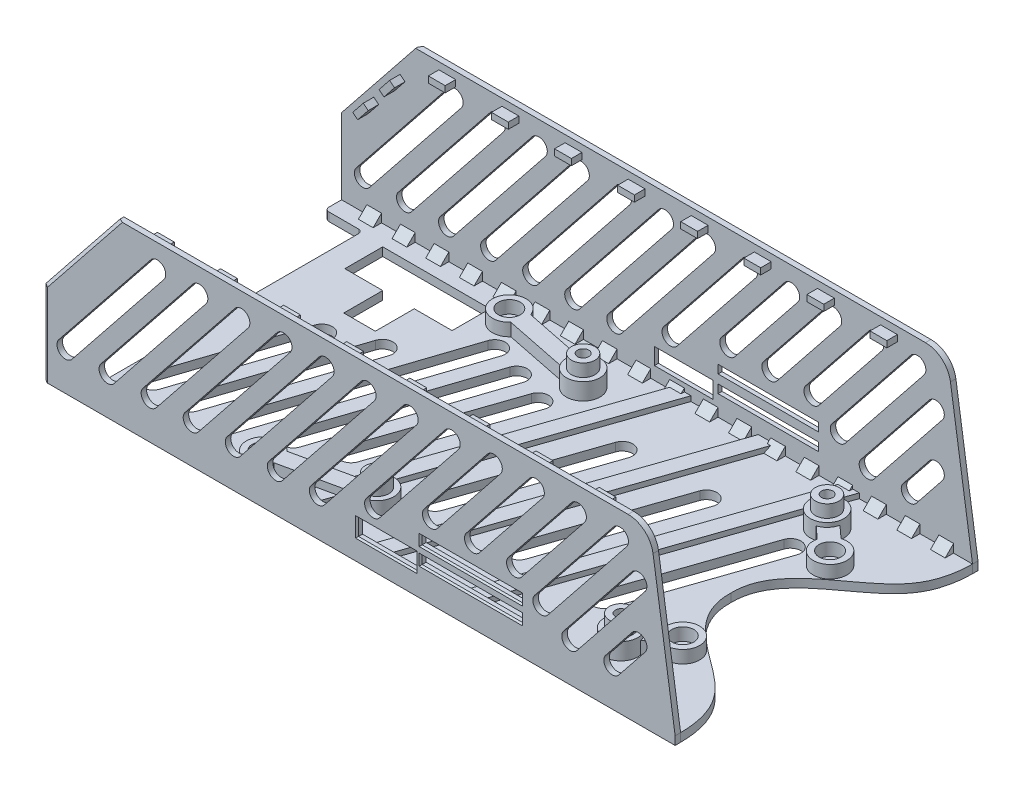
SolidWorks part; units mm, degrees
material "PPS"
ref_plane "前视基准面" through (0, 0, 0) normal (0, 0, 1) x (1, 0, 0)
ref_plane "上视基准面" through (0, 0, 0) normal (0, 1, 0) x (1, 0, 0)
ref_plane "右视基准面" through (0, 0, 0) normal (1, 0, 0) x (0, 0, -1)
sketch "草图1" plane through (0, 0, 0) normal (0, 1, 0) x (1, 0, 0)
  line L1 (-38.5883, 74.1339) -> (111.4117, 74.1339)
  line L2 (-38.5883, 74.1339) -> (-38.5883, 2.1339)
  line L3 (-38.5883, 2.1339) -> (111.4117, 2.1339)
  line L4 (111.4117, 74.1339) -> (111.4117, 2.1339)
  dimension "D1" = 72
  dimension "D2" = 150
extrude "底板" add sketch "草图1" against normal blind 2 contours L2 L1 L4 L3
sketch "草图2" plane through (0, 0, 0) normal (0, 1, 0) x (1, 0, 0)
  circle A3 centre (28.7548, 13.929) radius 4
  circle A4 centre (86.7548, 13.929) radius 4
  circle A5 centre (86.7548, 62.929) radius 4
  circle A6 centre (28.7548, 62.929) radius 4
  dimension "D1" = 2
  dimension "D2" = 2
extrude "板卡固定柱" add sketch "草图2" along normal blind 7
sketch "螺母孔" plane through (0, -2, 0) normal (0, -1, 0) x (1, 0, 0)
  line L0 (88.256, -11.329) -> (85.2537, -11.329)
  line L1 (30.256, -11.329) -> (27.2537, -11.329)
  line L2 (27.2537, -11.329) -> (25.7526, -13.929)
  line L3 (25.7526, -13.929) -> (27.2537, -16.529)
  line L4 (27.2537, -16.529) -> (30.256, -16.529)
  line L5 (30.256, -16.529) -> (31.7571, -13.929)
  line L6 (31.7571, -13.929) -> (30.256, -11.329)
  line L7 (85.2537, -11.329) -> (83.7526, -13.929)
  line L8 (83.7526, -13.929) -> (85.2537, -16.529)
  line L9 (85.2537, -16.529) -> (88.256, -16.529)
  line L10 (88.256, -16.529) -> (89.7571, -13.929)
  line L11 (89.7571, -13.929) -> (88.256, -11.329)
  line L12 (88.256, -60.329) -> (85.2537, -60.329)
  line L13 (85.2537, -60.329) -> (83.7526, -62.929)
  line L14 (83.7526, -62.929) -> (85.2537, -65.529)
  line L15 (85.2537, -65.529) -> (88.256, -65.529)
  line L16 (88.256, -65.529) -> (89.7571, -62.929)
  line L17 (89.7571, -62.929) -> (88.256, -60.329)
  line L18 (30.256, -60.329) -> (27.2537, -60.329)
  line L19 (27.2537, -60.329) -> (25.7526, -62.929)
  line L20 (25.7526, -62.929) -> (27.2537, -65.529)
  line L21 (27.2537, -65.529) -> (30.256, -65.529)
  line L22 (30.256, -65.529) -> (31.7571, -62.929)
  line L23 (31.7571, -62.929) -> (30.256, -60.329)
  circle A0 centre (28.7548, -13.929) radius 2.6 construction
  circle A1 centre (28.7548, -13.929) radius 4 construction
  circle A2 centre (86.7548, -13.929) radius 2.6 construction
  circle A3 centre (86.7548, -62.929) radius 2.6 construction
  circle A4 centre (28.7548, -62.929) radius 2.6 construction
  dimension "D1" = 2
  dimension "D2" = 2
extrude "m2.5螺母孔槽" cut sketch "螺母孔" against normal blind 5
sketch "草图4" plane through (0, 3, 0) normal (0, -1, 0) x (1, 0, 0)
  circle A0 centre (28.7548, -13.929) radius 1.35
  circle A1 centre (28.7548, -13.929) radius 4 construction
  circle A2 centre (86.7548, -13.929) radius 1.35
  circle A3 centre (86.7548, -62.929) radius 1.35
  circle A4 centre (28.7548, -62.929) radius 1.35
  dimension "D1" = 2
  dimension "D2" = 2
extrude "m2.5通孔" cut sketch "草图4" against normal up to next
sketch "草图6" plane through (0, 7, 0) normal (0, 1, 0) x (1, 0, 0)
  circle A0 centre (28.7548, 13.929) radius 4
  circle A1 centre (28.7548, 13.929) radius 2.7944
  circle A2 centre (86.7548, 13.929) radius 4
  circle A3 centre (86.7548, 13.929) radius 2.7944
  circle A4 centre (86.7548, 62.929) radius 4
  circle A5 centre (86.7548, 62.929) radius 2.7944
  circle A6 centre (28.7548, 62.929) radius 4
  circle A7 centre (28.7548, 62.929) radius 2.7944
  dimension "D1" = 2
  dimension "D2" = 2
extrude "切除-拉伸3" cut sketch "草图6" against normal blind 3
sketch "侧边" plane through (0, 0, -74.1339) normal (0, 0, -1) x (-1, 0, 0)
  line L0 (-74.7943, 6.8381) -> (-50.9153, 6.8381)
  line L1 (-111.4117, 0) -> (38.5883, 0)
  line L6 (-74.7943, 10.8959) -> (-50.9153, 10.8959)
  line L8 (-74.7943, 10.8959) -> (-74.7943, 8.8959)
  line L9 (-74.7943, 4.8381) -> (-50.9153, 4.8381)
  line L10 (-50.9153, 4.8381) -> (-50.9153, 6.8381)
  line L11 (-74.7943, 8.8959) -> (-50.9153, 8.8959)
  line L12 (-74.7943, 6.8381) -> (-74.7943, 4.8381)
  line L13 (-50.9153, 8.8959) -> (-50.9153, 10.8959)
  line L16 (-49.6686, 3.0554) -> (-35.7948, 3.0554)
  line L17 (-35.7948, 3.0554) -> (-35.7948, 7)
  line L18 (-35.7948, 7) -> (-49.6686, 7)
  line L19 (-49.6686, 7) -> (-49.6686, 3.0554)
  line L21 (38.5883, -2) -> (38.5883, 0) construction
  line L22 (20.9589, 40) -> (-100.2254, 40)
  line L23 (-106.1585, 34.8932) -> (-111.4117, 0)
  line L25 (38.5883, 0) -> (38.5883, 17.9447)
  line L26 (38.5883, 17.9447) -> (20.9589, 40)
  line L27 (33.5375, 7.0719) -> (11.6845, 34.4113) construction
  line L28 (31.9753, 5.8231) -> (10.1222, 33.1625)
  line L29 (35.0998, 8.3206) -> (13.2467, 35.66)
  line L30 (23.5375, 7.0719) -> (1.6845, 34.4113) construction
  line L31 (21.9753, 5.8231) -> (0.1222, 33.1625)
  line L32 (25.0998, 8.3206) -> (3.2467, 35.66)
  line L33 (13.5375, 7.0719) -> (-8.3155, 34.4113) construction
  line L34 (11.9753, 5.8231) -> (-9.8778, 33.1625)
  line L35 (15.0998, 8.3206) -> (-6.7533, 35.66)
  line L36 (3.5375, 7.0719) -> (-18.3155, 34.4113) construction
  line L37 (1.9753, 5.8231) -> (-19.8778, 33.1625)
  line L38 (5.0998, 8.3206) -> (-16.7533, 35.66)
  line L39 (-6.4625, 7.0719) -> (-28.3155, 34.4113) construction
  line L40 (-8.0247, 5.8231) -> (-29.8778, 33.1625)
  line L41 (-4.9002, 8.3206) -> (-26.7533, 35.66)
  line L42 (-16.4625, 7.0719) -> (-38.3155, 34.4113) construction
  line L43 (-18.0247, 5.8231) -> (-39.8778, 33.1625)
  line L44 (-14.9002, 8.3206) -> (-36.7533, 35.66)
  line L45 (-26.4625, 7.0719) -> (-48.3155, 34.4113) construction
  line L46 (-28.0247, 5.8231) -> (-49.8778, 33.1625)
  line L47 (-24.9002, 8.3206) -> (-46.7533, 35.66)
  line L48 (-39.5843, 10.9775) -> (-58.3155, 34.4113) construction
  line L49 (-41.1466, 9.7287) -> (-59.8778, 33.1625)
  line L50 (-38.0221, 12.2262) -> (-56.7533, 35.66)
  line L51 (-53.3306, 15.6642) -> (-68.3155, 34.4113) construction
  line L52 (-54.8928, 14.4155) -> (-69.8778, 33.1625)
  line L53 (-51.7683, 16.913) -> (-66.7533, 35.66)
  line L54 (-63.3306, 15.6642) -> (-78.3155, 34.4113) construction
  line L55 (-64.8928, 14.4155) -> (-79.8778, 33.1625)
  line L56 (-61.7683, 16.913) -> (-76.7533, 35.66)
  line L57 (-73.3306, 15.6642) -> (-88.3155, 34.4113) construction
  line L58 (-74.8928, 14.4155) -> (-89.8778, 33.1625)
  line L59 (-71.7683, 16.913) -> (-86.7533, 35.66)
  line L60 (-79.5843, 10.9775) -> (-98.3155, 34.4113) construction
  line L61 (-81.1466, 9.7287) -> (-99.8778, 33.1625)
  line L62 (-78.0221, 12.2262) -> (-96.7533, 35.66)
  line L63 (-86.4625, 7.0719) -> (-102.6962, 27.3811) construction
  line L64 (-88.0247, 5.8231) -> (-104.2584, 26.1324)
  line L65 (-84.9002, 8.3206) -> (-101.1339, 28.6299)
  line L66 (-96.4625, 7.0719) -> (-102.7062, 14.8831) construction
  line L67 (-98.0247, 5.8231) -> (-104.2685, 13.6344)
  line L68 (-94.9002, 8.3206) -> (-101.144, 16.1319)
  arc A0 (-100.2254, 40) -> (-106.1585, 34.8932) centre (-100.2254, 34) ccw
  arc A1 (31.9753, 5.8231) -> (35.0998, 8.3206) centre (33.5375, 7.0719) ccw
  arc A2 (13.2467, 35.66) -> (10.1222, 33.1625) centre (11.6845, 34.4113) ccw
  arc A3 (21.9753, 5.8231) -> (25.0998, 8.3206) centre (23.5375, 7.0719) ccw
  arc A4 (3.2467, 35.66) -> (0.1222, 33.1625) centre (1.6845, 34.4113) ccw
  arc A5 (11.9753, 5.8231) -> (15.0998, 8.3206) centre (13.5375, 7.0719) ccw
  arc A6 (-6.7533, 35.66) -> (-9.8778, 33.1625) centre (-8.3155, 34.4113) ccw
  arc A7 (1.9753, 5.8231) -> (5.0998, 8.3206) centre (3.5375, 7.0719) ccw
  arc A8 (-16.7533, 35.66) -> (-19.8778, 33.1625) centre (-18.3155, 34.4113) ccw
  arc A9 (-8.0247, 5.8231) -> (-4.9002, 8.3206) centre (-6.4625, 7.0719) ccw
  arc A10 (-26.7533, 35.66) -> (-29.8778, 33.1625) centre (-28.3155, 34.4113) ccw
  arc A11 (-18.0247, 5.8231) -> (-14.9002, 8.3206) centre (-16.4625, 7.0719) ccw
  arc A12 (-36.7533, 35.66) -> (-39.8778, 33.1625) centre (-38.3155, 34.4113) ccw
  arc A13 (-28.0247, 5.8231) -> (-24.9002, 8.3206) centre (-26.4625, 7.0719) ccw
  arc A14 (-46.7533, 35.66) -> (-49.8778, 33.1625) centre (-48.3155, 34.4113) ccw
  arc A15 (-41.1466, 9.7287) -> (-38.0221, 12.2262) centre (-39.5843, 10.9775) ccw
  arc A16 (-56.7533, 35.66) -> (-59.8778, 33.1625) centre (-58.3155, 34.4113) ccw
  arc A17 (-54.8928, 14.4155) -> (-51.7683, 16.913) centre (-53.3306, 15.6642) ccw
  arc A18 (-66.7533, 35.66) -> (-69.8778, 33.1625) centre (-68.3155, 34.4113) ccw
  arc A19 (-64.8928, 14.4155) -> (-61.7683, 16.913) centre (-63.3306, 15.6642) ccw
  arc A20 (-76.7533, 35.66) -> (-79.8778, 33.1625) centre (-78.3155, 34.4113) ccw
  arc A21 (-74.8928, 14.4155) -> (-71.7683, 16.913) centre (-73.3306, 15.6642) ccw
  arc A22 (-86.7533, 35.66) -> (-89.8778, 33.1625) centre (-88.3155, 34.4113) ccw
  arc A23 (-81.1466, 9.7287) -> (-78.0221, 12.2262) centre (-79.5843, 10.9775) ccw
  arc A24 (-96.7533, 35.66) -> (-99.8778, 33.1625) centre (-98.3155, 34.4113) ccw
  arc A25 (-88.0247, 5.8231) -> (-84.9002, 8.3206) centre (-86.4625, 7.0719) ccw
  arc A26 (-101.1339, 28.6299) -> (-104.2584, 26.1324) centre (-102.6962, 27.3811) ccw
  arc A27 (-98.0247, 5.8231) -> (-94.9002, 8.3206) centre (-96.4625, 7.0719) ccw
  arc A28 (-101.144, 16.1319) -> (-104.2685, 13.6344) centre (-102.7062, 14.8831) ccw
  point P2 (22.611, 20.7416)
  point P31 (12.611, 20.7416)
  point P38 (2.611, 20.7416)
  point P48 (-7.389, 20.7416)
  point P55 (-17.389, 20.7416)
  point P62 (-27.389, 20.7416)
  point P69 (-37.389, 20.7416)
  point P76 (-48.9499, 22.6944)
  point P83 (-60.8231, 25.0378)
  point P90 (-70.8231, 25.0378)
  point P97 (-80.8231, 25.0378)
  point P104 (-88.9499, 22.6944)
  point P111 (-94.5793, 17.2265)
  point P118 (-99.5843, 10.9775)
  dimension "D1" = 6
  dimension "D2" = 40
extrude "侧边凸台" add sketch "侧边" against normal blind 1.3
sketch "草图14" plane through (0, 0, -72.8339) normal (0, 0, 1) x (1, 0, 0)
  line L0 (-30.9262, 24.9677) -> (-33.4237, 21.8432)
  line L1 (-33.4237, 21.8432) -> (-32.2521, 20.9067)
  line L2 (-24.6825, 32.779) -> (-27.18, 29.6545)
  line L3 (-27.18, 29.6545) -> (-26.0083, 28.7179)
  line L4 (-26.0083, 28.7179) -> (-23.5108, 31.8424)
  line L5 (-23.5108, 31.8424) -> (-24.6825, 32.779)
  line L6 (-32.2521, 20.9067) -> (-29.7546, 24.0312)
  line L7 (-29.7546, 24.0312) -> (-30.9262, 24.9677)
  line L9 (-15.4544, 38.32) -> (-11.4544, 38.32)
  line L10 (-11.4544, 38.32) -> (-11.4544, 36.82)
  line L11 (-11.4544, 36.82) -> (-15.4544, 36.82)
  line L12 (-15.4544, 36.82) -> (-15.4544, 38.32)
  line L13 (-20.9589, 40) -> (100.2254, 40) construction
  line L14 (-0.4544, 38.32) -> (3.5456, 38.32)
  line L15 (3.5456, 38.32) -> (3.5456, 36.82)
  line L16 (3.5456, 36.82) -> (-0.4544, 36.82)
  line L17 (-0.4544, 36.82) -> (-0.4544, 38.32)
  line L18 (14.5456, 38.32) -> (18.5456, 38.32)
  line L19 (18.5456, 38.32) -> (18.5456, 36.82)
  line L20 (18.5456, 36.82) -> (14.5456, 36.82)
  line L21 (14.5456, 36.82) -> (14.5456, 38.32)
  line L22 (29.5456, 38.32) -> (33.5456, 38.32)
  line L23 (33.5456, 38.32) -> (33.5456, 36.82)
  line L24 (33.5456, 36.82) -> (29.5456, 36.82)
  line L25 (29.5456, 36.82) -> (29.5456, 38.32)
  line L26 (44.5456, 38.32) -> (48.5456, 38.32)
  line L27 (48.5456, 38.32) -> (48.5456, 36.82)
  line L28 (48.5456, 36.82) -> (44.5456, 36.82)
  line L29 (44.5456, 36.82) -> (44.5456, 38.32)
  line L30 (59.5456, 38.32) -> (63.5456, 38.32)
  line L31 (63.5456, 38.32) -> (63.5456, 36.82)
  line L32 (63.5456, 36.82) -> (59.5456, 36.82)
  line L33 (59.5456, 36.82) -> (59.5456, 38.32)
  line L34 (74.5456, 38.32) -> (78.5456, 38.32)
  line L35 (78.5456, 38.32) -> (78.5456, 36.82)
  line L36 (78.5456, 36.82) -> (74.5456, 36.82)
  line L37 (74.5456, 36.82) -> (74.5456, 38.32)
  line L38 (89.5456, 38.32) -> (93.5456, 38.32)
  line L39 (93.5456, 38.32) -> (93.5456, 36.82)
  line L40 (93.5456, 36.82) -> (89.5456, 36.82)
  line L41 (89.5456, 36.82) -> (89.5456, 38.32)
  dimension "D1" = 2
  dimension "D2" = 1.68
  dimension "D3" = 1.5
  dimension "D4" = 4
  dimension "D5" = 8
extrude "顶盖支架" add sketch "草图14" along normal blind 2.5
sketch "草图15" plane through (0, -2, 0) normal (0, -1, 0) x (1, 0, 0)
  line L0 (-38.5883, -38.1339) -> (111.4117, -38.1339)
  line L1 (-38.5883, -74.1339) -> (-38.5883, -2.1339) construction
  line L2 (111.4117, -74.1339) -> (111.4117, -2.1339) construction
ref_plane "基准面7" through (0, 0, -38.1339) normal (0, 0, -1) x (-1, 0, 0)
mirror "镜向1" about plane through (0, 0, -38.1339) normal (0, 0, -1) of "侧边凸台", "顶盖支架"
sketch "草图17" plane through (0, -2, 0) normal (0, -1, 0) x (1, 0, 0)
  line L0 (-7.5175, -59.0417) -> (1.4825, -59.0417)
  line L1 (1.4825, -59.0417) -> (1.4825, -68.0417)
  line L6 (1.4825, -68.0417) -> (-24.0175, -68.0417)
  line L7 (-24.0175, -68.0417) -> (-24.0175, -59.0417)
  line L8 (-24.0175, -59.0417) -> (-15.0175, -59.0417)
  line L9 (6.7325, -8.8917) -> (6.7325, -67.3917)
  line L10 (6.7325, -67.3917) -> (6.7325, -38.1417)
  line L11 (-7.5175, -49.7917) -> (-15.0175, -49.7917)
  line L12 (-7.5175, -59.0417) -> (-7.5175, -49.7917)
  line L14 (-15.0175, -49.7917) -> (-15.0175, -59.0417)
  line L15 (6.7325, -38.1417) -> (17.9206, -38.1417)
  circle A6 centre (6.7325, -67.3917) radius 1.55
  circle A7 centre (94.7325, -55.6417) radius 1.55
  circle A8 centre (6.7325, -67.3917) radius 1.55
  circle A9 centre (94.7325, -20.6417) radius 1.55
  circle A10 centre (6.7325, -8.8917) radius 1.55
  dimension "D1" = 9
  dimension "D2" = 9
  dimension "D3" = 9
  dimension "D4" = 58.5
extrude "链接孔" cut sketch "草图17" against normal blind 2.5 contours A6 | L11 L14 L12 | A7 | A9 | A10 region at (-11.2675, -2, -61.4236) region at (7.7975, -2, -66.3267)
sketch "草图18" plane through (0, 0, 0) normal (0, 1, 0) x (1, 0, 0)
  line L0 (-38.5883, 7.4339) -> (-38.5883, 68.8339)
  line L13 (-23.5883, 13.0192) -> (-13.5883, 43.1339) construction
  line L14 (23.1, 38.1339) -> (-23.1, 38.1339) construction
  line L15 (-25.9609, 13.8071) -> (-15.9609, 43.9218)
  line L22 (-21.2157, 12.2314) -> (-11.2157, 42.3461)
  line L23 (-38.5883, 7.4339) -> (-30.5883, 7.4339)
  line L24 (-29.5883, 8.4339) -> (-29.5883, 67.8339)
  line L25 (-30.5883, 68.8339) -> (-38.5883, 68.8339)
  line L26 (-38.5883, 38.1339) -> (111.4117, 38.1339) construction
  line L27 (-14.5883, 13.0192) -> (-3.2431, 47.1848) construction
  line L28 (-16.9609, 13.8071) -> (-5.6157, 47.9727)
  line L29 (-12.2157, 12.2314) -> (-0.8705, 46.3969)
  line L30 (-5.5883, 13.0192) -> (10.1689, 60.4714) construction
  line L31 (-7.9609, 13.8071) -> (7.7963, 61.2593)
  line L32 (-3.2157, 12.2314) -> (12.5415, 59.6836)
  line L33 (4.9874, 17.7644) -> (18.2234, 57.6243) construction
  line L34 (2.6148, 18.5523) -> (15.8508, 58.4121)
  line L35 (7.36, 16.9766) -> (20.596, 56.8364)
  line L36 (14.9242, 21.5786) -> (26.2679, 54.6893) construction
  line L37 (12.5591, 22.3889) -> (23.9029, 55.4996)
  line L38 (17.2892, 20.7683) -> (28.633, 53.879)
  line L39 (111.4117, 72.8339) -> (-38.5883, 72.8339) construction
  line L41 (111.4117, 72.8339) -> (111.4117, 3.4339)
  line L44 (34.9242, 21.5786) -> (46.2679, 54.6893) construction
  line L45 (32.5591, 22.3889) -> (43.9029, 55.4996)
  line L46 (37.2892, 20.7683) -> (48.633, 53.879)
  line L50 (54.9242, 21.5786) -> (66.2679, 54.6893) construction
  line L51 (52.5591, 22.3889) -> (63.9029, 55.4996)
  line L52 (57.2892, 20.7683) -> (68.633, 53.879)
  line L56 (74.9242, 21.5786) -> (86.2679, 54.6893) construction
  line L57 (72.5591, 22.3889) -> (83.9029, 55.4996)
  line L58 (77.2892, 20.7683) -> (88.633, 53.879)
  line L156 (44.9242, 21.5786) -> (56.2679, 54.6893) construction
  line L157 (42.5591, 22.3889) -> (53.9029, 55.4996)
  line L158 (47.2892, 20.7683) -> (58.633, 53.879)
  line L159 (64.9242, 21.5786) -> (76.2679, 54.6893) construction
  line L160 (62.5591, 22.3889) -> (73.9029, 55.4996)
  line L161 (67.2892, 20.7683) -> (78.633, 53.879)
  line L162 (24.9242, 21.5786) -> (36.2679, 54.6893) construction
  line L163 (22.5591, 22.3889) -> (33.9029, 55.4996)
  line L164 (27.2892, 20.7683) -> (38.633, 53.879)
  line L165 (44.9242, 21.5786) -> (56.2679, 54.6893) construction
  line L166 (42.5591, 22.3889) -> (53.9029, 55.4996)
  line L167 (47.2892, 20.7683) -> (58.633, 53.879)
  line L168 (64.9242, 21.5786) -> (76.2679, 54.6893) construction
  line L169 (62.5591, 22.3889) -> (73.9029, 55.4996)
  line L170 (67.2892, 20.7683) -> (78.633, 53.879)
  line L171 (24.9242, 21.5786) -> (36.2679, 54.6893) construction
  line L172 (22.5591, 22.3889) -> (33.9029, 55.4996)
  line L173 (27.2892, 20.7683) -> (38.633, 53.879)
  arc A2 (-25.9609, 13.8071) -> (-21.2157, 12.2314) centre (-23.5883, 13.0192) ccw
  arc A3 (-11.2157, 42.3461) -> (-15.9609, 43.9218) centre (-13.5883, 43.1339) ccw
  arc A4 (-16.9609, 13.8071) -> (-12.2157, 12.2314) centre (-14.5883, 13.0192) ccw
  arc A5 (-0.8705, 46.3969) -> (-5.6157, 47.9727) centre (-3.2431, 47.1848) ccw
  arc A6 (-7.9609, 13.8071) -> (-3.2157, 12.2314) centre (-5.5883, 13.0192) ccw
  arc A7 (12.5415, 59.6836) -> (7.7963, 61.2593) centre (10.1689, 60.4714) ccw
  arc A8 (2.6148, 18.5523) -> (7.36, 16.9766) centre (4.9874, 17.7644) ccw
  arc A9 (20.596, 56.8364) -> (15.8508, 58.4121) centre (18.2234, 57.6243) ccw
  arc A10 (12.5591, 22.3889) -> (17.2892, 20.7683) centre (14.9242, 21.5786) ccw
  arc A11 (28.633, 53.879) -> (23.9029, 55.4996) centre (26.2679, 54.6893) ccw
  arc A18 (-30.5883, 7.4339) -> (-29.5883, 8.4339) centre (-30.5883, 8.4339) ccw
  arc A19 (-29.5883, 67.8339) -> (-30.5883, 68.8339) centre (-30.5883, 67.8339) ccw
  arc A21 (32.5591, 22.3889) -> (37.2892, 20.7683) centre (34.9242, 21.5786) ccw
  arc A22 (48.633, 53.879) -> (43.9029, 55.4996) centre (46.2679, 54.6893) ccw
  arc A25 (52.5591, 22.3889) -> (57.2892, 20.7683) centre (54.9242, 21.5786) ccw
  arc A26 (68.633, 53.879) -> (63.9029, 55.4996) centre (66.2679, 54.6893) ccw
  arc A29 (72.5591, 22.3889) -> (77.2892, 20.7683) centre (74.9242, 21.5786) ccw
  arc A30 (88.633, 53.879) -> (83.9029, 55.4996) centre (86.2679, 54.6893) ccw
  arc A102 (42.5591, 22.3889) -> (47.2892, 20.7683) centre (44.9242, 21.5786) ccw
  arc A103 (58.633, 53.879) -> (53.9029, 55.4996) centre (56.2679, 54.6893) ccw
  arc A104 (62.5591, 22.3889) -> (67.2892, 20.7683) centre (64.9242, 21.5786) ccw
  arc A105 (78.633, 53.879) -> (73.9029, 55.4996) centre (76.2679, 54.6893) ccw
  arc A106 (22.5591, 22.3889) -> (27.2892, 20.7683) centre (24.9242, 21.5786) ccw
  arc A107 (38.633, 53.879) -> (33.9029, 55.4996) centre (36.2679, 54.6893) ccw
  spline S0 degree 3 poles (111.4117, 72.8339) (111.3592, 67.7048) (109.4998, 62.8559) (100.5415, 53.3454) (88.3796, 48.3908) (88.633, 38.1339) knots 0 0 0 0 0.239028 0.339028 1 1 1 1
  spline S1 degree 3 poles (111.4117, 3.4339) (111.3592, 8.5631) (109.4998, 13.412) (100.5415, 22.9225) (88.3796, 27.8771) (88.633, 38.1339) knots 0 0 0 0 0.239028 0.339028 1 1 1 1
  point P0 (0, 0)
  point P6 (50.596, 38.1339)
  point P20 (-18.5883, 28.0766)
  point P31 (-8.9157, 30.102)
  point P38 (2.2903, 36.7453)
  point P44 (40.596, 38.1339)
  point P47 (11.6054, 37.6944)
  point P54 (20.596, 38.1339)
  point P65 (30.596, 38.1339)
  point P68 (28.7548, 38.1339)
  point P72 (70.596, 38.1339)
  point P82 (-29.5883, 7.4339)
  point P87 (60.596, 38.1339)
  point P101 (80.596, 38.1339)
  point P109 (50.596, 38.1339)
  point P116 (70.596, 38.1339)
  point P123 (30.596, 38.1339)
  point P130 (50.596, 38.1339)
  point P137 (70.596, 38.1339)
  point P144 (30.596, 38.1339)
  point P151 (50.596, 38.1339)
  point P158 (70.596, 38.1339)
  point P165 (30.596, 38.1339)
  point P172 (50.596, 38.1339)
  point P179 (70.596, 38.1339)
  point P186 (30.596, 38.1339)
  point P193 (50.596, 38.1339)
  point P200 (70.596, 38.1339)
  point P207 (30.596, 38.1339)
  point P214 (50.596, 38.1339)
  point P221 (70.596, 38.1339)
  point P228 (30.596, 38.1339)
  point P235 (50.596, 38.1339)
  point P242 (70.596, 38.1339)
  point P249 (30.596, 38.1339)
  point P256 (50.596, 38.1339)
  point P263 (70.596, 38.1339)
  point P270 (30.596, 38.1339)
  point P277 (50.596, 38.1339)
  point P284 (70.596, 38.1339)
  point P291 (30.596, 38.1339)
  point P298 (50.596, 38.1339)
  point P305 (70.596, 38.1339)
  point P312 (30.596, 38.1339)
  point P319 (50.596, 38.1339)
  point P326 (70.596, 38.1339)
  point P333 (30.596, 38.1339)
  point P340 (50.596, 38.1339)
  point P347 (70.596, 38.1339)
  point P354 (30.596, 38.1339)
  dimension "D8" = 2.5
  dimension "D1" = 0
  dimension "D2" = 7
  dimension "D6" = 9
  dimension "D7" = 6
  dimension "D9" = 5
  dimension "D10" = 16
  dimension "D11" = 12.3625
extrude "切除-拉伸6" cut sketch "草图18" against normal up to next
fillet "圆角3" radius 1 2 edges at (-38.5883, -1, -7.4339) (-38.5883, -1, -68.8339)
sketch "草图21" plane through (0, 0, 0) normal (0, 1, 0) x (1, 0, 0)
  line L19 (24.9625, 61.6568) -> (9.7304, 64.7436)
  line L21 (25.757, 65.5771) -> (10.5248, 68.6639)
  line L24 (24.9468, 14.8691) -> (9.6967, 11.5776)
  line L26 (25.7907, 10.9592) -> (10.5406, 7.6676)
  line L32 (90.7942, 19.9417) -> (88.1178, 17.6896)
  line L33 (93.3696, 16.8811) -> (90.6931, 14.629)
  line L36 (87.9636, 59.116) -> (90.826, 56.5014)
  line L38 (90.6614, 62.0693) -> (93.5237, 59.4547)
  arc A12 (10.5248, 68.6639) -> (9.7304, 64.7436) centre (6.7325, 67.3917) ccw
  circle A13 centre (6.7325, 67.3917) radius 2.6
  arc A14 (25.757, 65.5771) -> (24.9625, 61.6568) centre (28.7548, 62.929) ccw
  arc A15 (9.6967, 11.5776) -> (10.5406, 7.6676) centre (6.7325, 8.8917) ccw
  circle A16 centre (6.7325, 8.8917) radius 2.6
  arc A17 (24.9468, 14.8691) -> (25.7907, 10.9592) centre (28.7548, 13.645) ccw
  arc A18 (93.3696, 16.8811) -> (90.7942, 19.9417) centre (94.7325, 20.6417) ccw
  circle A19 centre (94.7325, 20.6417) radius 2.6
  arc A20 (90.6931, 14.629) -> (88.1178, 17.6896) centre (86.7548, 13.929) ccw
  arc A21 (90.826, 56.5014) -> (93.5237, 59.4547) centre (94.7325, 55.6417) ccw
  circle A22 centre (94.7325, 55.6417) radius 2.6
  arc A23 (87.9636, 59.116) -> (90.6614, 62.0693) centre (86.7548, 62.929) ccw
extrude "板卡固定加强筋" add sketch "草图21" along normal blind 3
sketch "草图23" plane through (0, 0, 0) normal (0, 1, 0) x (1, 0, 0)
  line L0 (111.4117, 72.8339) -> (-38.5883, 72.8339) construction
  line L1 (-32.5883, 72.8339) -> (-29.0883, 72.8339)
  line L2 (-32.5883, 72.8339) -> (-32.5883, 70.8339)
  line L3 (-32.5883, 70.8339) -> (-29.0883, 70.8339)
  line L4 (-29.0883, 72.8339) -> (-29.0883, 70.8339)
  line L5 (-24.5883, 72.8339) -> (-24.5883, 70.8339)
  line L6 (-24.5883, 72.8339) -> (-21.0883, 72.8339)
  line L7 (-24.5883, 70.8339) -> (-21.0883, 70.8339)
  line L8 (-21.0883, 72.8339) -> (-21.0883, 70.8339)
  line L9 (-16.5883, 72.8339) -> (-16.5883, 70.8339)
  line L10 (-16.5883, 72.8339) -> (-13.0883, 72.8339)
  line L11 (-16.5883, 70.8339) -> (-13.0883, 70.8339)
  line L12 (-13.0883, 72.8339) -> (-13.0883, 70.8339)
  line L13 (-8.5883, 72.8339) -> (-8.5883, 70.8339)
  line L14 (-8.5883, 72.8339) -> (-5.0883, 72.8339)
  line L15 (-8.5883, 70.8339) -> (-5.0883, 70.8339)
  line L16 (-5.0883, 72.8339) -> (-5.0883, 70.8339)
  line L17 (-0.5883, 72.8339) -> (-0.5883, 70.8339)
  line L18 (-0.5883, 72.8339) -> (2.9117, 72.8339)
  line L19 (-0.5883, 70.8339) -> (2.9117, 70.8339)
  line L20 (2.9117, 72.8339) -> (2.9117, 70.8339)
  line L21 (7.4117, 72.8339) -> (7.4117, 70.8339)
  line L22 (7.4117, 72.8339) -> (10.9117, 72.8339)
  line L23 (7.4117, 70.8339) -> (10.9117, 70.8339)
  line L24 (10.9117, 72.8339) -> (10.9117, 70.8339)
  line L25 (15.4117, 72.8339) -> (15.4117, 70.8339)
  line L26 (15.4117, 72.8339) -> (18.9117, 72.8339)
  line L27 (15.4117, 70.8339) -> (18.9117, 70.8339)
  line L28 (18.9117, 72.8339) -> (18.9117, 70.8339)
  line L29 (23.4117, 72.8339) -> (23.4117, 70.8339)
  line L30 (23.4117, 72.8339) -> (26.9117, 72.8339)
  line L31 (23.4117, 70.8339) -> (26.9117, 70.8339)
  line L32 (26.9117, 72.8339) -> (26.9117, 70.8339)
  line L33 (31.4117, 72.8339) -> (31.4117, 70.8339)
  line L34 (31.4117, 72.8339) -> (34.9117, 72.8339)
  line L35 (31.4117, 70.8339) -> (34.9117, 70.8339)
  line L36 (34.9117, 72.8339) -> (34.9117, 70.8339)
  line L37 (39.4117, 72.8339) -> (39.4117, 70.8339)
  line L38 (39.4117, 72.8339) -> (42.9117, 72.8339)
  line L39 (39.4117, 70.8339) -> (42.9117, 70.8339)
  line L40 (42.9117, 72.8339) -> (42.9117, 70.8339)
  line L41 (47.4117, 72.8339) -> (47.4117, 70.8339)
  line L42 (47.4117, 72.8339) -> (50.9117, 72.8339)
  line L43 (47.4117, 70.8339) -> (50.9117, 70.8339)
  line L44 (50.9117, 72.8339) -> (50.9117, 70.8339)
  line L45 (55.4117, 72.8339) -> (55.4117, 70.8339)
  line L46 (55.4117, 72.8339) -> (58.9117, 72.8339)
  line L47 (55.4117, 70.8339) -> (58.9117, 70.8339)
  line L48 (58.9117, 72.8339) -> (58.9117, 70.8339)
  line L49 (63.4117, 72.8339) -> (63.4117, 70.8339)
  line L50 (63.4117, 72.8339) -> (66.9117, 72.8339)
  line L51 (63.4117, 70.8339) -> (66.9117, 70.8339)
  line L52 (66.9117, 72.8339) -> (66.9117, 70.8339)
  line L53 (71.4117, 72.8339) -> (71.4117, 70.8339)
  line L54 (71.4117, 72.8339) -> (74.9117, 72.8339)
  line L55 (71.4117, 70.8339) -> (74.9117, 70.8339)
  line L56 (74.9117, 72.8339) -> (74.9117, 70.8339)
  line L57 (79.4117, 72.8339) -> (79.4117, 70.8339)
  line L58 (79.4117, 72.8339) -> (82.9117, 72.8339)
  line L59 (79.4117, 70.8339) -> (82.9117, 70.8339)
  line L60 (82.9117, 72.8339) -> (82.9117, 70.8339)
  line L61 (87.4117, 72.8339) -> (87.4117, 70.8339)
  line L62 (87.4117, 72.8339) -> (90.9117, 72.8339)
  line L63 (87.4117, 70.8339) -> (90.9117, 70.8339)
  line L64 (90.9117, 72.8339) -> (90.9117, 70.8339)
  line L65 (95.4117, 72.8339) -> (95.4117, 70.8339)
  line L66 (95.4117, 72.8339) -> (98.9117, 72.8339)
  line L67 (95.4117, 70.8339) -> (98.9117, 70.8339)
  line L68 (98.9117, 72.8339) -> (98.9117, 70.8339)
  line L69 (103.4117, 72.8339) -> (103.4117, 70.8339)
  line L70 (103.4117, 72.8339) -> (106.9117, 72.8339)
  line L71 (103.4117, 70.8339) -> (106.9117, 70.8339)
  line L72 (106.9117, 72.8339) -> (106.9117, 70.8339)
  line L73 (23.1, 38.1339) -> (-23.1, 38.1339) construction
  line L74 (106.9117, 3.4339) -> (106.9117, 5.4339)
  line L75 (103.4117, 5.4339) -> (106.9117, 5.4339)
  line L76 (103.4117, 3.4339) -> (106.9117, 3.4339)
  line L77 (103.4117, 3.4339) -> (103.4117, 5.4339)
  line L78 (98.9117, 3.4339) -> (98.9117, 5.4339)
  line L79 (95.4117, 5.4339) -> (98.9117, 5.4339)
  line L80 (95.4117, 3.4339) -> (98.9117, 3.4339)
  line L81 (95.4117, 3.4339) -> (95.4117, 5.4339)
  line L82 (90.9117, 3.4339) -> (90.9117, 5.4339)
  line L83 (87.4117, 5.4339) -> (90.9117, 5.4339)
  line L84 (87.4117, 3.4339) -> (90.9117, 3.4339)
  line L85 (87.4117, 3.4339) -> (87.4117, 5.4339)
  line L86 (82.9117, 3.4339) -> (82.9117, 5.4339)
  line L87 (79.4117, 5.4339) -> (82.9117, 5.4339)
  line L88 (79.4117, 3.4339) -> (82.9117, 3.4339)
  line L89 (79.4117, 3.4339) -> (79.4117, 5.4339)
  line L90 (74.9117, 3.4339) -> (74.9117, 5.4339)
  line L91 (71.4117, 5.4339) -> (74.9117, 5.4339)
  line L92 (71.4117, 3.4339) -> (74.9117, 3.4339)
  line L93 (71.4117, 3.4339) -> (71.4117, 5.4339)
  line L94 (66.9117, 3.4339) -> (66.9117, 5.4339)
  line L95 (63.4117, 5.4339) -> (66.9117, 5.4339)
  line L96 (63.4117, 3.4339) -> (66.9117, 3.4339)
  line L97 (63.4117, 3.4339) -> (63.4117, 5.4339)
  line L98 (58.9117, 3.4339) -> (58.9117, 5.4339)
  line L99 (55.4117, 5.4339) -> (58.9117, 5.4339)
  line L100 (55.4117, 3.4339) -> (58.9117, 3.4339)
  line L101 (55.4117, 3.4339) -> (55.4117, 5.4339)
  line L102 (50.9117, 3.4339) -> (50.9117, 5.4339)
  line L103 (47.4117, 5.4339) -> (50.9117, 5.4339)
  line L104 (47.4117, 3.4339) -> (50.9117, 3.4339)
  line L105 (47.4117, 3.4339) -> (47.4117, 5.4339)
  line L106 (42.9117, 3.4339) -> (42.9117, 5.4339)
  line L107 (39.4117, 5.4339) -> (42.9117, 5.4339)
  line L108 (39.4117, 3.4339) -> (42.9117, 3.4339)
  line L109 (39.4117, 3.4339) -> (39.4117, 5.4339)
  line L110 (34.9117, 3.4339) -> (34.9117, 5.4339)
  line L111 (31.4117, 5.4339) -> (34.9117, 5.4339)
  line L112 (31.4117, 3.4339) -> (34.9117, 3.4339)
  line L113 (31.4117, 3.4339) -> (31.4117, 5.4339)
  line L114 (26.9117, 3.4339) -> (26.9117, 5.4339)
  line L115 (23.4117, 5.4339) -> (26.9117, 5.4339)
  line L116 (23.4117, 3.4339) -> (26.9117, 3.4339)
  line L117 (23.4117, 3.4339) -> (23.4117, 5.4339)
  line L118 (18.9117, 3.4339) -> (18.9117, 5.4339)
  line L119 (15.4117, 5.4339) -> (18.9117, 5.4339)
  line L120 (15.4117, 3.4339) -> (18.9117, 3.4339)
  line L121 (15.4117, 3.4339) -> (15.4117, 5.4339)
  line L122 (10.9117, 3.4339) -> (10.9117, 5.4339)
  line L123 (7.4117, 5.4339) -> (10.9117, 5.4339)
  line L124 (7.4117, 3.4339) -> (10.9117, 3.4339)
  line L125 (7.4117, 3.4339) -> (7.4117, 5.4339)
  line L126 (2.9117, 3.4339) -> (2.9117, 5.4339)
  line L127 (-0.5883, 5.4339) -> (2.9117, 5.4339)
  line L128 (-0.5883, 3.4339) -> (2.9117, 3.4339)
  line L129 (-0.5883, 3.4339) -> (-0.5883, 5.4339)
  line L130 (-5.0883, 3.4339) -> (-5.0883, 5.4339)
  line L131 (-8.5883, 5.4339) -> (-5.0883, 5.4339)
  line L132 (-8.5883, 3.4339) -> (-5.0883, 3.4339)
  line L133 (-8.5883, 3.4339) -> (-8.5883, 5.4339)
  line L134 (-13.0883, 3.4339) -> (-13.0883, 5.4339)
  line L135 (-16.5883, 5.4339) -> (-13.0883, 5.4339)
  line L136 (-16.5883, 3.4339) -> (-13.0883, 3.4339)
  line L137 (-16.5883, 3.4339) -> (-16.5883, 5.4339)
  line L138 (-21.0883, 3.4339) -> (-21.0883, 5.4339)
  line L139 (-24.5883, 5.4339) -> (-21.0883, 5.4339)
  line L140 (-24.5883, 3.4339) -> (-21.0883, 3.4339)
  line L141 (-24.5883, 3.4339) -> (-24.5883, 5.4339)
  line L142 (-29.0883, 3.4339) -> (-29.0883, 5.4339)
  line L143 (-32.5883, 5.4339) -> (-29.0883, 5.4339)
  line L144 (-32.5883, 3.4339) -> (-32.5883, 5.4339)
  line L145 (-32.5883, 3.4339) -> (-29.0883, 3.4339)
  dimension "D1" = 6
  dimension "D2" = 3.5
  dimension "D3" = 2
  dimension "D4" = 18
extrude "凸台-拉伸7" add sketch "草图23" along normal blind 2.5
chamfer "倒角1" distance 2.5 angle 45 36 edges at (-30.8383, 2.5, -70.8339) (-22.8383, 2.5, -5.4339) (-30.8383, 2.5, -5.4339) (-14.8383, 2.5, -5.4339) (-6.8383, 2.5, -5.4339) (1.1617, 2.5, -5.4339) (9.8276, 2.5, -5.4339) (17.1617, 2.5, -5.4339) (25.1617, 2.5, -5.4339) (33.1617, 2.5, -5.4339) (41.1617, 2.5, -5.4339) (49.1617, 2.5, -5.4339) (57.1617, 2.5, -5.4339) (65.1617, 2.5, -5.4339) (73.1617, 2.5, -5.4339) (81.1617, 2.5, -5.4339) (89.1617, 2.5, -5.4339) (97.1617, 2.5, -5.4339) (105.1617, 2.5, -5.4339) (105.1617, 2.5, -70.8339) (97.1617, 2.5, -70.8339) (89.1617, 2.5, -70.8339) (81.1617, 2.5, -70.8339) (73.1617, 2.5, -70.8339) (65.1617, 2.5, -70.8339) (57.1617, 2.5, -70.8339) (49.1617, 2.5, -70.8339) (41.1617, 2.5, -70.8339) (33.1617, 2.5, -70.8339) (25.1617, 2.5, -70.8339) (17.1617, 2.5, -70.8339) (9.8408, 2.5, -70.8339) (1.1617, 2.5, -70.8339) (-6.8383, 2.5, -70.8339) (-14.8383, 2.5, -70.8339) (-22.8383, 2.5, -70.8339)
sketch "草图25" plane through (0, 0, 0) normal (0, 1, 0) x (1, 0, 0)
  line L8 (84.4843, 72.8339) -> (80.4843, 72.8339)
  line L10 (60.7078, 3.4339) -> (56.7078, 3.4339)
  line L11 (64.4843, 72.8339) -> (60.4843, 72.8339)
  line L12 (40.7078, 3.4339) -> (36.7078, 3.4339)
  line L13 (84.4843, 72.8339) -> (60.7078, 3.4339)
  line L14 (64.4843, 72.8339) -> (40.7078, 3.4339)
  line L15 (80.4843, 72.8339) -> (56.7078, 3.4339)
  line L16 (60.4843, 72.8339) -> (36.7078, 3.4339)
  line L17 (44.4843, 72.8339) -> (40.4843, 72.8339)
  line L18 (20.7078, 3.4339) -> (16.7078, 3.4339)
  line L19 (44.4843, 72.8339) -> (20.7078, 3.4339)
  line L20 (40.4843, 72.8339) -> (16.7078, 3.4339)
  dimension "D1" = 3
extrude "凸台-拉伸8" add sketch "草图25" along normal blind 1.2
sketch "草图10" plane through (0, 0, -72.8339) normal (0, 0, 1) x (1, 0, 0)
  circle A0 centre (95.5627, 14.116) radius 3.7
sketch "草图8" plane through (0, 0, 0) normal (0, 1, 0) x (1, 0, 0)
  line L0 (86.7548, 62.929) -> (28.7548, 13.929)
  line L1 (28.7548, 13.929) -> (28.7548, 62.929)
  line L2 (28.7548, 62.929) -> (86.7548, 13.929)
  line L3 (86.7548, 13.929) -> (86.7548, 62.929)
chamfer "倒角2" distance 0.75 angle 30 4 edges at (-38.5883, 7.9723, -74.1339) (-29.7736, 28.9723, -74.1339) (-38.5883, 7.9723, -2.1339) (-29.7736, 28.9723, -2.1339) first distance on face at (-38.5883, 5.3149, -72.2673) first distance on face at (-29.7736, 28.9723, -73.4839) first distance on face at (47.4314, 18.5627, -2.1339)
chamfer "倒角3" distance 0.35 angle 45 24 edges at (35.7948, 5.0277, -74.1339) (42.7317, 3.0554, -74.1339) (49.6686, 5.0277, -74.1339) (42.7317, 7, -74.1339) (74.7943, 5.8381, -74.1339) (62.8548, 4.8381, -74.1339) (50.9153, 5.8381, -74.1339) (62.8548, 6.8381, -74.1339) (62.8548, 8.8959, -74.1339) (50.9153, 9.8959, -74.1339) (62.8548, 10.8959, -74.1339) (74.7943, 9.8959, -74.1339) (74.7943, 5.8381, -2.1339) (62.8548, 6.8381, -2.1339) (62.8548, 4.8381, -2.1339) (50.9153, 5.8381, -2.1339) (74.7943, 9.8959, -2.1339) (62.8548, 8.8959, -2.1339) (50.9153, 9.8959, -2.1339) (62.8548, 10.8959, -2.1339) (42.7317, 3.0554, -2.1339) (35.7948, 5.0277, -2.1339) (49.6686, 5.0277, -2.1339) (42.7317, 7, -2.1339)
